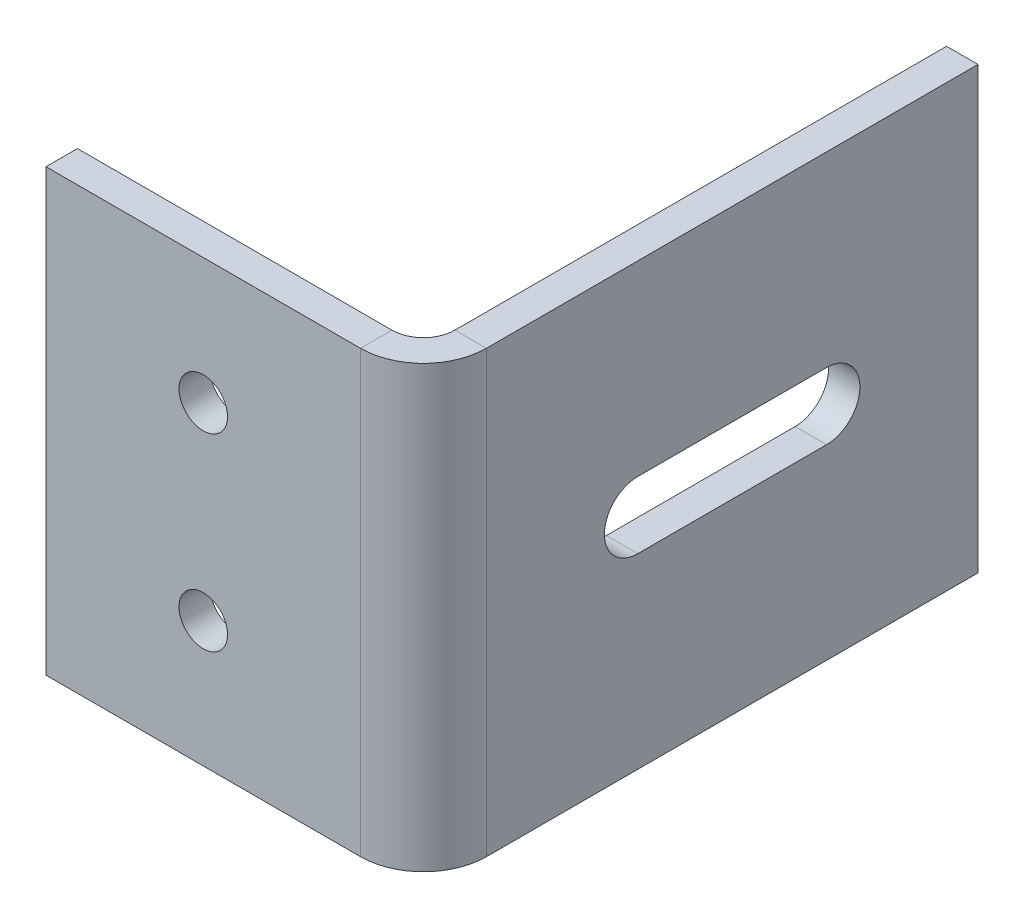
SolidWorks part; units mm, degrees
note: The reader was unsure of these and kept them because the rebuilt part matched: thickness of "Base-Flange1", "Edge-Flange1", "Sheet-Metal1", "Sheet-Metal2", "Sheet-Metal3", "Sheet-Metal6"; flange length of "Edge-Flange1".
material "5052-H32"
ref_plane "Front Plane" through (0, 0, 0) normal (0, 0, 1) x (1, 0, 0)
ref_plane "Top Plane" through (0, 0, 0) normal (0, 1, 0) x (1, 0, 0)
ref_plane "Right Plane" through (0, 0, 0) normal (1, 0, 0) x (0, 0, -1)
sketch "Sketch1" plane through (0, 0, 0) normal (0, 0, 1) x (1, 0, 0)
  line L1 (-19.05, 22.225) -> (19.05, 22.225)
  line L2 (-19.05, 22.225) -> (-19.05, -22.225)
  line L3 (-19.05, -22.225) -> (19.05, -22.225)
  line L4 (19.05, 22.225) -> (19.05, -22.225)
  line L5 (-19.05, 22.225) -> (19.05, -22.225) construction
  line L6 (-19.05, -22.225) -> (19.05, 22.225) construction
  point P0 (0, 0)
  dimension "D1" = 44.45
  dimension "D2" = 38.1
base flange "Base-Flange1" sketch "Sketch1" thickness 3.175 reverse thickness direction no parameters "D1"=0.7366
edge flange "Edge-Flange1" sketch "Sketch8" flange angle 90 flange length 55.9816 flange position material inside bend radius 3.175 thickness 3.175 relief rectangular parameters "D6"=10
sketch "Sketch8" plane through (19.05, 0, -3.175) normal (1, 0, 0) x (0, -1, 0)
  line L2 (-22.225, 0) -> (-22.225, 52.8066)
  line L3 (-22.225, 52.8066) -> (22.225, 52.8066)
  line L4 (22.225, 52.8066) -> (22.225, 0)
  line L7 (22.225, 0) -> (-22.225, 0) construction
  line L8 (22.225, 0) -> (-22.225, 0)
  dimension "D1" = 52.8066
bend "EdgeBend1" bend radius 3.175 bend angle 90 parameters "D5"=1
sketch "Sketch9" plane through (0, 0, -3.175) normal (0, 0, -1) x (-1, 0, 0)
  line L0 (-12.7, 22.225) -> (19.05, 22.225) construction
  line L1 (19.05, -22.225) -> (-12.7, -22.225) construction
  line L2 (19.05, 22.225) -> (19.05, -22.225) construction
  circle A0 centre (3.175, 9.525) radius 2.4511
  circle A1 centre (3.175, -9.525) radius 2.4511
  dimension "D1" = 4.9022
  dimension "D2" = 4.9022
  dimension "D3" = 12.7
  dimension "D4" = 12.7
  dimension "D5" = 15.875
  dimension "D6" = 15.875
extrude "Cut-Extrude1" cut sketch "Sketch9" against normal through all normal cut yes
sketch "Sketch12" plane through (15.875, 0, 0) normal (-1, 0, 0) x (0, 0, 1)
  line L0 (-40.6908, 0) -> (-21.6408, 0) construction
  line L1 (-40.6908, 3.3734) -> (-21.6408, 3.3734)
  line L2 (-40.6908, -3.3734) -> (-21.6408, -3.3734)
  line L3 (-6.35, -22.225) -> (-55.9816, -22.225) construction
  arc A1 (-40.6908, 3.3734) -> (-40.6908, -3.3734) centre (-40.6908, 0) ccw
  arc A2 (-21.6408, -3.3734) -> (-21.6408, 3.3734) centre (-21.6408, 0) ccw
  point P3 (-31.1658, 0)
  point P10 (-31.1658, -22.225)
  dimension "D1" = 3.3734
  dimension "D2" = 19.05
extrude "Cut-Extrude3" cut sketch "Sketch12" against normal through all normal cut yes
sketch "Bend-Lines1" [suppressed] plane through (0, 0, 0) normal (0, 1, 0) x (1, 0, 0)
sketch "Bounding-Box1" [suppressed] plane through (0, 0, 0) normal (0, 1, 0) x (1, 0, 0)
sheet metal parameters "Sheet-Metal1" thickness 3.175 parameters "D1"=0.7366
flat pattern "Flat-Pattern1" [suppressed]
sketch "Bend-Lines2" plane through (0, 0, 0) normal (0, 1, 0) x (1, 0, 0)
sketch3d "Bounding-Box2" [suppressed]
  line L0 (38.1, -22.225, 0) -> (-38.1, -22.225, 0) construction
  line L1 (38.1, 22.225, 0) -> (-38.1, 22.225, 0) construction
  line L2 (38.1, -22.225, 0) -> (38.1, 22.225, 0) construction
  line L3 (-38.1, -22.225, 0) -> (-38.1, 22.225, 0) construction
sheet metal parameters "Sheet-Metal2" thickness 3.175 parameters "D1"=0.7366, "D7"=0.9144
flat pattern "Flat-Pattern1"
sketch "Bend-Lines2" plane through (0, 0, 0) normal (0, 0, 1) x (1, 0, 0)
  line L0 (16.4405, -22.225) -> (16.4405, 22.225) construction
  line L1 (16.4405, -22.225) -> (16.4405, 22.225) construction
sketch3d "Bounding-Box2" [suppressed]
  line L0 (-19.05, -22.225, 0) -> (60.5415, -22.225, 0) construction
  line L1 (-19.05, 22.225, 0) -> (60.5415, 22.225, 0) construction
  line L2 (-19.05, -22.225, 0) -> (-19.05, 22.225, 0) construction
  line L3 (60.5415, -22.225, 0) -> (60.5415, 22.225, 0) construction
bend of the flat pattern "Flatten-<EdgeBend1>1"
sheet metal parameters "Sheet-Metal3" thickness 3.175 parameters "D1"=0.7366, "D7"=0.9144
flat pattern "Flat-Pattern1" [suppressed]
sketch "Bend-Lines2" plane through (0, 0, 0) normal (0, 0, 1) x (1, 0, 0)
  line L0 (16.4405, -22.225) -> (16.4405, 22.225) construction
  line L1 (16.4405, -22.225) -> (16.4405, 22.225) construction
sketch3d "Bounding-Box2" [suppressed]
  line L0 (-19.05, -22.225, 0) -> (69.8125, -22.225, 0) construction
  line L1 (-19.05, 22.225, 0) -> (69.8125, 22.225, 0) construction
  line L2 (-19.05, -22.225, 0) -> (-19.05, 22.225, 0) construction
  line L3 (69.8125, -22.225, 0) -> (69.8125, 22.225, 0) construction
bend of the flat pattern "Flatten-<EdgeBend1>1"
sketch "Sketch10-1" [suppressed] plane through (13.8309, 0, -3.175) normal (0, 0, -1) x (-1, 0, 0)
  line L0 (-55.9816, -22.225) -> (-55.9816, 22.225) construction
  line L1 (32.8809, -22.225) -> (-55.9816, -22.225) construction
  circle A0 centre (-33.7566, 0) radius 3.3734
  dimension "D3" = 6.7469
  dimension "D1" = 22.225
  dimension "D2" = 22.225
sheet metal parameters "Sheet-Metal6" thickness 3.175 parameters "D1"=0.7366, "D7"=0.9144
flat pattern "Flat-Pattern1"
sketch "Bend-Lines2" plane through (0, 0, 0) normal (0, 0, 1) x (1, 0, 0)
  line L0 (16.4405, -22.225) -> (16.4405, 22.225) construction
  line L1 (16.4405, -22.225) -> (16.4405, 22.225) construction
sketch3d "Bounding-Box2" [suppressed]
  line L0 (-19.05, -22.225, 0) -> (69.8125, -22.225, 0) construction
  line L1 (-19.05, 22.225, 0) -> (69.8125, 22.225, 0) construction
  line L2 (-19.05, -22.225, 0) -> (-19.05, 22.225, 0) construction
  line L3 (69.8125, -22.225, 0) -> (69.8125, 22.225, 0) construction
bend of the flat pattern "Flatten-<EdgeBend1>1"
